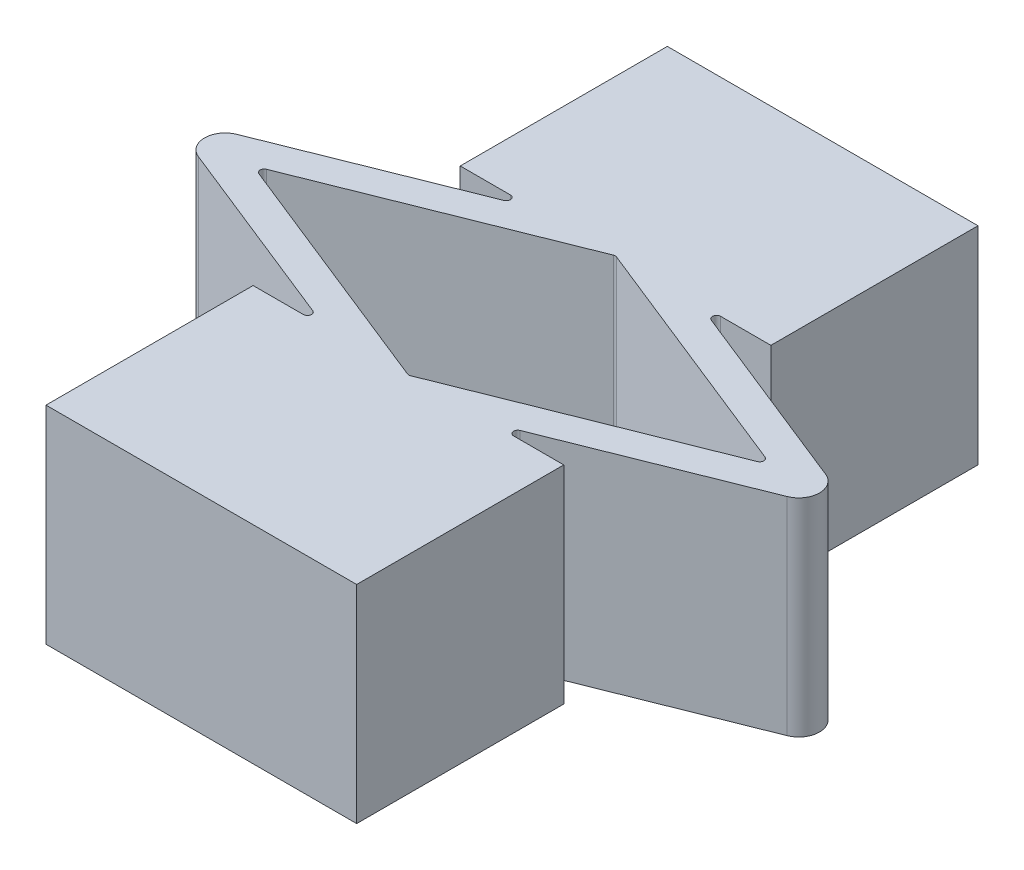
SolidWorks part; units mm, degrees
ref_plane "Front Plane" through (0, 0, 0) normal (0, 0, 1) x (1, 0, 0)
ref_plane "Top Plane" through (0, 0, 0) normal (0, 1, 0) x (1, 0, 0)
ref_plane "Right Plane" through (0, 0, 0) normal (1, 0, 0) x (0, 0, -1)
sketch "Sketch1" plane through (0, 0, 0) normal (0, 1, 0) x (1, 0, 0)
  line L0 (0, 15) -> (-12.5, 10)
  line L1 (-7.5, -5) -> (7.5, -5)
  line L2 (-7.5, -5) -> (-7.5, 5)
  line L3 (-7.5, 5) -> (7.5, 5)
  line L4 (7.5, -5) -> (7.5, 5)
  line L5 (-7.5, -5) -> (7.5, 5) construction
  line L6 (-7.5, 5) -> (7.5, -5) construction
  line L7 (-7.5, 15) -> (7.5, 15)
  line L8 (-7.5, 15) -> (-7.5, 25)
  line L9 (-7.5, 25) -> (7.5, 25)
  line L10 (7.5, 15) -> (7.5, 25)
  line L11 (-7.5, 15) -> (7.5, 25) construction
  line L12 (-7.5, 25) -> (7.5, 15) construction
  line L13 (-12.5, 10) -> (0, 5)
  line L14 (-4.0389, 15) -> (-16.5389, 10)
  line L15 (-16.5389, 10) -> (-4.0389, 5)
  line L16 (0, 20) -> (0, 0) construction
  point P0 (0, 0)
  point P6 (0, 20)
  point P17 (0, 10)
  point P20 (0, 0)
  dimension "D1" = 10
  dimension "D2" = 15
  dimension "D3" = 10
  dimension "D4" = 15
  dimension "D5" = 20
  dimension "D6" = 25
  dimension "D7" = 1.5
extrude "Boss-Extrude2" add sketch "Sketch1" along normal blind 10 contours L7 L10 L9 L8 | L1 L4 L3 L2 region at (0, 0, -20) region at (0, 0, 0)
extrude "Boss-Extrude3" add sketch "Sketch1<4>" along normal blind 10 contours L14 L15 L3 L13 L0 L7 region at (-6.3218, 0, -12.6794)
sketch "Sketch1<4>" plane through (0, 0, 0) normal (0, 1, 0) x (1, 0, 0) same geometry as "Sketch1"
ref_plane "Plane1" through (0, 0, 0) normal (-1, 0, 0) x (0, 0, 1)
mirror "Mirror1" about plane through (0, 0, 0) normal (-1, 0, 0) of "Boss-Extrude3"
fillet "Fillet1" radius 0.2 8 edges at (4.0389, 5, -5) (4.0389, 5, -15) (-4.0389, 5, -15) (-4.0389, 5, -5) (0, 5, -5) (12.5, 5, -10) (0, 5, -15) (-12.5, 5, -10)
fillet "Fillet2" radius 1 2 edges at (16.5389, 5, -10) (-16.5389, 5, -10)
